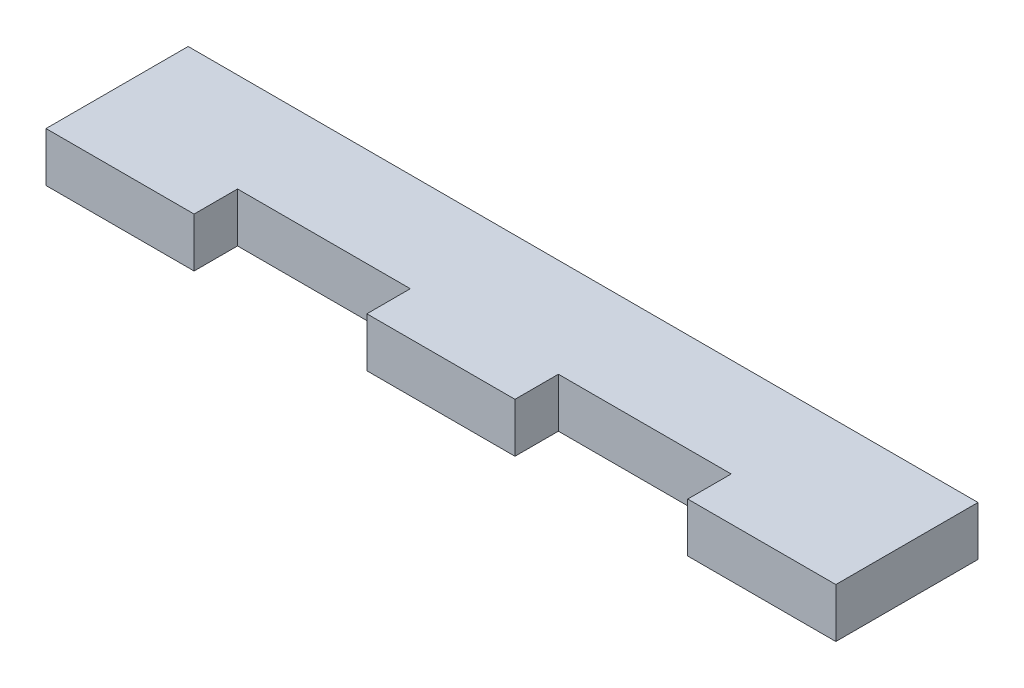
SolidWorks part; units mm, degrees
ref_plane "Front Plane" through (0, 0, 0) normal (0, 0, 1) x (1, 0, 0)
ref_plane "Top Plane" through (0, 0, 0) normal (0, 1, 0) x (1, 0, 0)
ref_plane "Right Plane" through (0, 0, 0) normal (1, 0, 0) x (0, 0, -1)
sketch "Sketch1" plane through (0, 0, 0) normal (0, 1, 0) x (1, 0, 0)
  line L0 (-9.525, -6.35) -> (-9.525, -11.938)
  line L1 (-31.75, -6.35) -> (-9.525, -6.35)
  line L2 (-50.8, -6.35) -> (-50.8, 6.35)
  line L3 (-50.8, 6.35) -> (50.8, 6.35)
  line L4 (50.8, -6.35) -> (50.8, 6.35)
  line L5 (-50.8, -6.35) -> (50.8, 6.35) construction
  line L6 (-50.8, 6.35) -> (50.8, -6.35) construction
  line L7 (9.525, -6.35) -> (31.75, -6.35)
  line L8 (-50.8, -6.35) -> (-50.8, -11.938)
  line L9 (-50.8, -11.938) -> (-31.75, -11.938)
  line L10 (-31.75, -6.35) -> (-31.75, -11.938)
  line L11 (-9.525, -11.938) -> (9.525, -11.938)
  line L12 (9.525, -6.35) -> (9.525, -11.938)
  line L13 (31.75, -6.35) -> (31.75, -11.938)
  line L14 (31.75, -11.938) -> (50.8, -11.938)
  line L15 (50.8, -6.35) -> (50.8, -11.938)
  point P0 (0, 0)
  dimension "D1" = 101.6
  dimension "D2" = 12.7
  dimension "D3" = 5.588
  dimension "D4" = 19.05
  dimension "D5" = 3
extrude "Boss-Extrude1" add sketch "Sketch1" along normal blind 6.35
